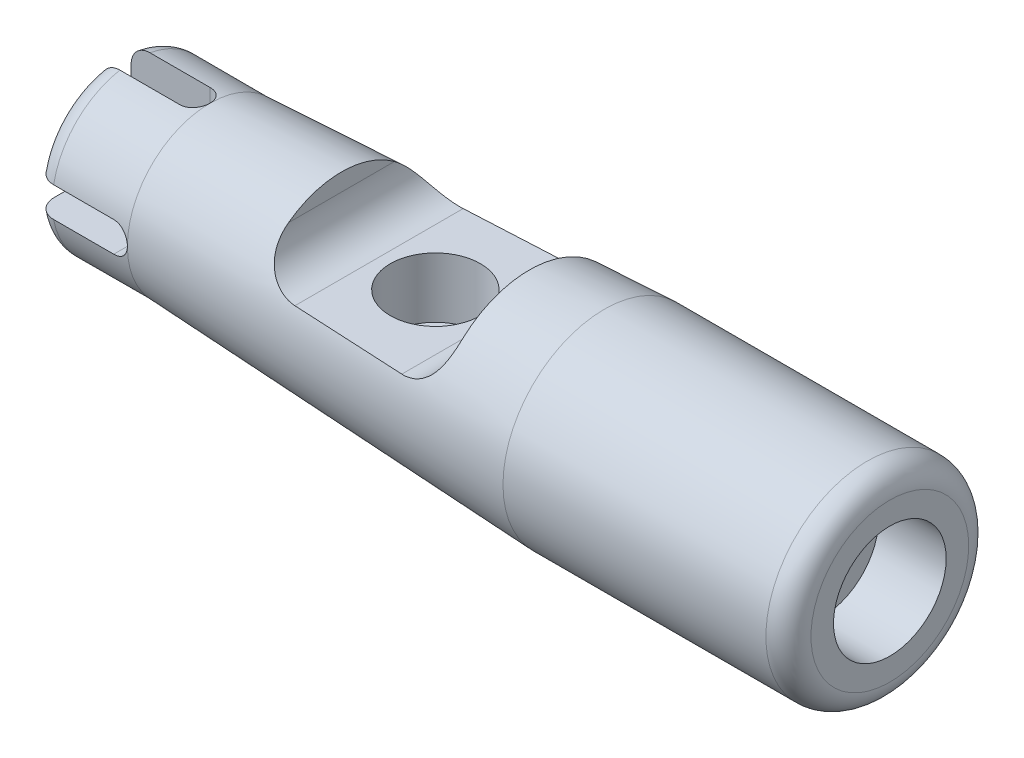
SolidWorks part; units mm, degrees
ref_plane "Front Plane" through (0, 0, 0) normal (0, 0, 1) x (1, 0, 0)
ref_plane "Top Plane" through (0, 0, 0) normal (0, 1, 0) x (1, 0, 0)
ref_plane "Right Plane" through (0, 0, 0) normal (1, 0, 0) x (0, 0, -1)
sketch "Sketch1" plane through (0, 0, 0) normal (0, 0, 1) x (1, 0, 0)
  line L0 (0, 0) -> (0, 27)
  line L1 (0, 0) -> (-206, 0)
  line L2 (-206, 0) -> (-206, 22)
  line L3 (-206, 22) -> (-181, 22)
  line L4 (-181, 22) -> (-76, 27)
  line L5 (-76, 27) -> (0, 27)
  dimension "D1" = 27
  dimension "D2" = 22
  dimension "D3" = 76
  dimension "D4" = 25
  dimension "D5" = 105
revolve "Revolve1" add sketch "Sketch1" angle 360 about L1
sketch "Sketch2" plane through (0, 0, 0) normal (0, 0, 1) x (1, 0, 0)
  line L0 (-206, 0) -> (-181, 0) construction
  line L1 (-206, 22) -> (-206, -22) construction
  line L2 (-181, 22) -> (-181, -22) construction
  line L3 (-206, 0) -> (-185, 0) construction
  line L4 (-206, 4) -> (-185, 4)
  line L5 (-206, -4) -> (-185, -4)
  arc A0 (-206, 4) -> (-206, -4) centre (-206, 0) ccw
  arc A1 (-185, -4) -> (-185, 4) centre (-185, 0) ccw
  point P8 (-195.5, 0)
  dimension "D1" = 4
extrude "Cut-Extrude1" cut sketch "Sketch2" against normal through all both and the other way through all
fillet "Fillet1" radius 5 2 edges at (-206, -22, 0) (-206, 22, 0)
pattern_circular "CirPattern1" count 2 every 90 about axis through (0, 0, 0) along (1, 0, 0) of "Cut-Extrude1"
sketch "Sketch5" plane through (0, 0, 0) normal (1, 0, 0) x (0, 0, -1)
  point P0 (0, 0)
sketch "Sketch9" plane through (0, 0, 0) normal (1, 0, 0) x (0, 0, -1)
  point P0 (0, 0)
hole_wizard "CBORE for M30 Hex Head Bolt2" positions "Sketch9" profile "Sketch8" counterbore size "M30" standard "ANSI Metric"
sketch "Sketch8" plane through (0, 0, 0) normal (0, 1, 0) x (0, 0, -1)
  line L0 (0, 0) -> (0, 41.6052)
  line L1 (0, 41.6052) -> (6, 38)
  line L2 (6, 38) -> (6, 18)
  line L3 (6, 18) -> (15, 18)
  line L4 (15, 18) -> (15, 0)
  line L5 (15, 0) -> (0, 0)
  line L10 (0, 41.6052) -> (-6, 38) construction
  line L11 (0, -6.35) -> (0, 107.95) construction
  dimension "Hole Dia." = 12
  dimension "Hole Depth" = 38
  dimension "C'Bore Dia." = 30
  dimension "C'Bore Depth" = 18
  dimension "Drill Angle" = 118
fillet "Fillet2" radius 6 1 edges at (0, 0, -27)
sketch "Sketch10" plane through (0, 0, 0) normal (0, 0, 1) x (1, 0, 0)
  line L0 (-76, -27) -> (-6, -27) construction
  line L1 (-16, -27) -> (-76, -27)
  line L2 (-16, -27) -> (-16, -22)
  line L3 (-16, -22) -> (-76, -22)
  line L4 (-76, -27) -> (-76, -22)
  line L5 (0, -21) -> (0, 21) construction
  dimension "D1" = 60
  dimension "D2" = 16
  dimension "D3" = 5
extrude "Cut-Extrude2" cut sketch "Sketch10" against normal through all both and the other way through all
fillet "Fillet3" radius 5 2 edges at (-16, -22, 0) (-76, -22, 0)
sketch "Sketch11" plane through (0, -22, 0) normal (0, -1, 0) x (1, 0, 0)
  line L0 (0, 0) -> (-43.5711, 0) construction
  line L1 (0, -15) -> (0, 15) construction
  line L2 (0, -21) -> (0, 21) construction
  circle A0 centre (-46, 12) radius 3
  circle A1 centre (-46, -12) radius 3
  dimension "D1" = 6
  dimension "D2" = 6
  dimension "D3" = 12
  dimension "D4" = 12
  dimension "D5" = 46
  dimension "D6" = 46
extrude "Cut-Extrude3" cut sketch "Sketch11" against normal blind 12 and the other way through all
sketch "Sketch12" plane through (0, 0, 0) normal (0, 0, 1) x (1, 0, 0)
  line L0 (-76, -27) -> (-76, 27) construction
  line L1 (-96, 27) -> (-146, 27)
  line L2 (-96, 27) -> (-96, 9)
  line L3 (-96, 9) -> (-146, 9)
  line L4 (-146, 27) -> (-146, 9)
  line L5 (-6, 27) -> (-76, 27) construction
  dimension "D1" = 50
  dimension "D2" = 18
  dimension "D3" = 20
extrude "Cut-Extrude4" cut sketch "Sketch12" against normal through all both and the other way through all
fillet "Fillet4" radius 10 2 edges at (-96, 9, 0) (-146, 9, 0)
sketch "Sketch13" plane through (0, 9, 0) normal (0, 1, 0) x (1, 0, 0)
  line L0 (-76, 27) -> (-76, -27) construction
  circle A0 centre (-121, 0) radius 12
  dimension "D1" = 24
  dimension "D2" = 45
extrude "Cut-Extrude5" cut sketch "Sketch13" against normal blind 16
